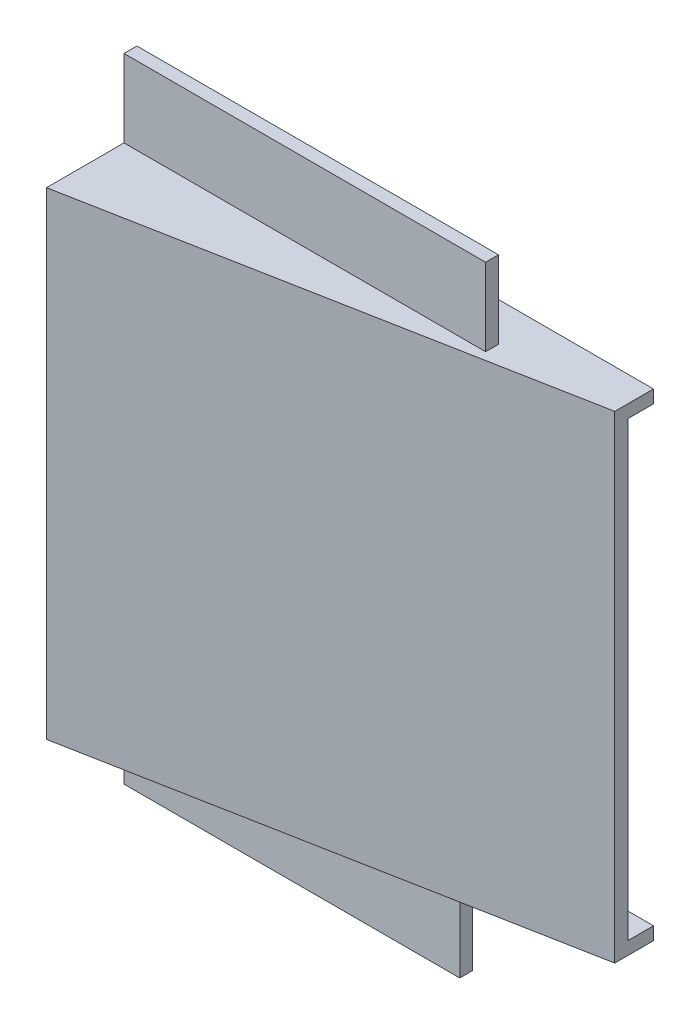
SolidWorks part; units mm, degrees
ref_plane "Front Plane" through (0, 0, 0) normal (0, 0, 1) x (1, 0, 0)
ref_plane "Top Plane" through (0, 0, 0) normal (0, 1, 0) x (1, 0, 0)
ref_plane "Right Plane" through (0, 0, 0) normal (1, 0, 0) x (0, 0, -1)
sketch "Sketch1" plane through (0, 0, 0) normal (0, 0, 1) x (1, 0, 0)
  line L1 (0, 0) -> (185, 0)
  line L2 (0, 0) -> (0, -185)
  line L3 (0, -185) -> (185, -185)
  line L4 (185, 0) -> (185, -185)
  dimension "D1" = 185
  dimension "D2" = 185
extrude "Boss-Extrude1" add sketch "Sketch1" along normal blind 50
sketch "Sketch8" plane through (0, -185, 0) normal (0, -1, 0) x (1, 0, 0)
  line L0 (0, 50) -> (185, 15)
  line L1 (185, 50) -> (185, 0) construction
  line L2 (185, 15) -> (185, 50)
  line L3 (185, 50) -> (0, 50)
  dimension "D1" = 15
extrude "Cut-Extrude1" cut sketch "Sketch8" against normal blind 190
sketch "Sketch9" plane through (0, -185, 0) normal (0, -1, 0) x (1, 0, 0)
  line L0 (185, 9.9113) -> (5, 43.9654)
  line L1 (5, 43.9654) -> (5, 0)
  line L2 (0, 0) -> (185, 0) construction
  line L3 (0, 50) -> (0, 0) construction
  line L4 (185, 15) -> (185, 0) construction
  line L5 (0, 50) -> (185, 15) construction
  line L6 (5, 0) -> (185, 0)
  line L7 (185, 0) -> (185, 9.9113)
  dimension "D1" = 5
  dimension "D2" = 5
  dimension "D3" = 5
extrude "Cut-Extrude3" cut sketch "Sketch9" against normal blind 175 from offset 5 offset against normal yes
sketch "Sketch10" plane through (0, -185, 0) normal (0, -1, 0) x (1, 0, 0)
  line L0 (0, 50) -> (0, 0) construction
  line L1 (0, 20) -> (130, 20)
  line L2 (0, 20) -> (0, 15)
  line L3 (0, 15) -> (130, 15)
  line L4 (130, 20) -> (130, 15)
  line L5 (0, 0) -> (185, 0) construction
  dimension "D1" = 15
  dimension "D2" = 5
  dimension "D3" = 130
extrude "Boss-Extrude2" add sketch "Sketch10" along normal blind 30
sketch "Sketch11" plane through (0, 0, 0) normal (0, 1, 0) x (1, 0, 0)
  line L5 (0, -50) -> (0, 0) construction
  line L6 (0, -15) -> (140, -15)
  line L7 (0, -15) -> (0, -20)
  line L8 (0, -20) -> (140, -20)
  line L9 (140, -15) -> (140, -20)
  line L10 (185, 0) -> (0, 0) construction
  dimension "D1" = 15
  dimension "D2" = 5
  dimension "D3" = 140
extrude "Boss-Extrude3" add sketch "Sketch11" along normal blind 30
